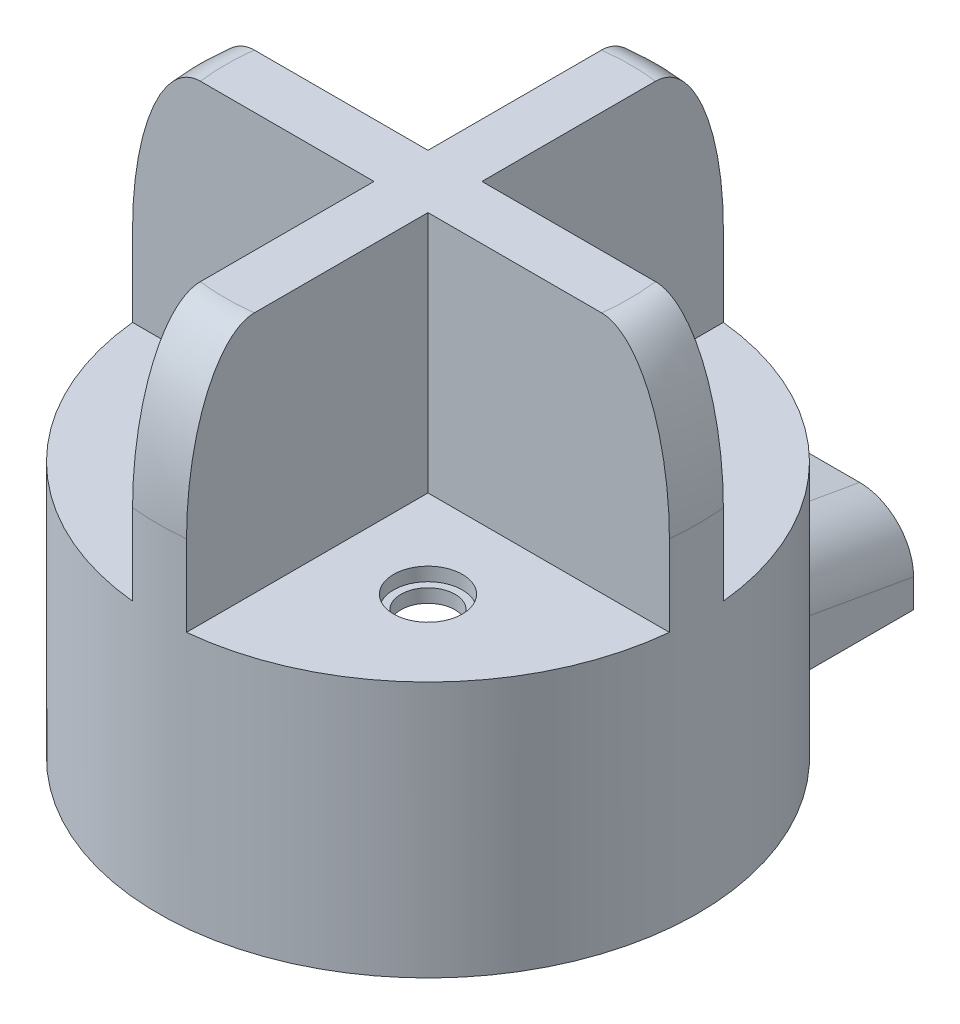
SolidWorks part; units mm, degrees
ref_plane "Front Plane" through (0, 0, 0) normal (0, 0, 1) x (1, 0, 0)
ref_plane "Top Plane" through (0, 0, 0) normal (0, 1, 0) x (1, 0, 0)
ref_plane "Right Plane" through (0, 0, 0) normal (1, 0, 0) x (0, 0, -1)
sketch "Sketch1" plane through (0, 0, 0) normal (0, 1, 0) x (1, 0, 0)
  line L0 (0, 20) -> (0, -20) construction
  line L1 (-20, 0) -> (20, 0) construction
  line L2 (-2, 20) -> (-2, 2)
  line L3 (-20, -2) -> (-2, -2)
  line L4 (2, 20) -> (2, 2)
  line L5 (-20, 2) -> (-2, 2)
  line L6 (2, 2) -> (20, 2)
  line L7 (-20, 2) -> (20, 2) construction
  line L8 (-2, -2) -> (-2, -20)
  line L9 (-2, 20) -> (-2, -20) construction
  line L10 (2, -2) -> (2, -20)
  line L11 (2, 20) -> (2, -20) construction
  line L12 (2, -2) -> (20, -2)
  line L13 (-20, -2) -> (20, -2) construction
  circle A0 centre (0, 0) radius 20
  point P6 (0, 0)
  point P9 (0, 0)
  dimension "D1" = 40
  dimension "D2" = 2
  dimension "D3" = 2
extrude "Boss-Extrude1" add sketch "Sketch1" along normal blind 2 contours A0
extrude "Boss-Extrude2" add sketch "Sketch1<3>" along normal blind 20 contours L12 A0 L6 L4 L2 L5 L3 L8 L10 region at (0, 0, 0)
sketch "Sketch1<3>" plane through (0, 0, 0) normal (0, 1, 0) x (1, 0, 0) same geometry as "Sketch1"
fillet "Fillet1" radius 12 4 edges at (-20, 20, 0) (0, 20, -20) (0, 20, 20) (20, 20, 0) second distance 5 first distance on face at (0, 0, 20)
sketch "Sketch2" plane through (0, 0, 0) normal (0, -1, 0) x (1, 0, 0)
  circle A2 centre (0, 0) radius 19
  circle A3 centre (0, 0) radius 19
  circle A4 centre (0, 0) radius 20
  circle A5 centre (0, 0) radius 20
  dimension "D1" = 1
  dimension "D2" = 0
extrude "Boss-Extrude3" add sketch "Sketch2" along normal blind 17
sketch "Sketch3" plane through (0, -17, 0) normal (0, -1, 0) x (1, 0, 0)
  line L0 (0, 20) -> (0, -20)
  circle A0 centre (0, 0) radius 20 construction
  circle A2 centre (0, 0) radius 20
  arc A3 (0, -20) -> (0, 20) centre (0, 0) ccw
  dimension "D1" = 0
extrude "Boss-Extrude4" [suppressed] add sketch "Sketch3" against normal blind 2
sketch "Sketch4" plane through (0, 2, 0) normal (0, 1, 0) x (1, 0, 0)
  line L0 (19.8997, -2) -> (2, -2) construction
  line L1 (2, -19.8997) -> (2, -2) construction
  line L2 (0, 6.0536) -> (0, 0) construction
  line L3 (0, 0) -> (5.728, 0) construction
  line L4 (-2, 14.8661) -> (-2, 2) construction
  line L5 (-2, 6.6454) -> (2, 6.6454)
  line L6 (2, 14.8661) -> (2, 2) construction
  circle A0 centre (8.5, -8.5) radius 2.55
  circle A1 centre (8.5, 8.5) radius 2.55
  circle A2 centre (-8.5, 8.5) radius 2.55
  circle A3 centre (-8.5, -8.5) radius 2.55
  dimension "D1" = 5.1
  dimension "D2" = 6.5
  dimension "D3" = 6.5
extrude "Cut-Extrude1" cut sketch "Sketch4" against normal blind 1 contours A3 | A0 | A1 | A2 region at (8.5, 2, 8.5) region at (8.5, 2, -8.5) region at (-8.5, 2, 8.5)
sketch "Sketch5" plane through (0, 0, 0) normal (0, 0, 1) x (1, 0, 0)
  line L0 (-20, -17) -> (20, -17) construction
  line L1 (-7.5, -10.5) -> (7.5, -10.5)
  line L2 (-7.5, -10.5) -> (-7.5, -17)
  line L3 (-7.5, -17) -> (7.5, -17)
  line L4 (7.5, -10.5) -> (7.5, -17)
  line L5 (-7.5, -10.5) -> (7.5, -17) construction
  line L6 (-7.5, -17) -> (7.5, -10.5) construction
  point P0 (0, -13.75)
  dimension "D1" = 15
  dimension "D2" = 6.5
extrude "Cut-Extrude2" cut sketch "Sketch5" against normal up to next
sketch "Sketch7" plane through (-7.5, 0, 0) normal (1, 0, 0) x (0, 0, -1)
  line L0 (17, -8.971) -> (27.5, -10.8225)
  line L2 (27.5, -10.8225) -> (27.5, -11.8225)
  line L3 (27.5, -11.8225) -> (17, -9.971)
  line L4 (17, -9.971) -> (17, -8.971)
  line L5 (20, -10.5) -> (20, 8) construction
  line L7 (18.5405, -10.5) -> (20, -10.5) construction
  dimension "D1" = 3
  dimension "D2" = 7.5
  dimension "D3" = 10
  dimension "D4" = 1
extrude "Boss-Extrude6" add sketch "Sketch7" along normal up to surface (15 mm away) up to face at (7.5, -13.75, -17.9988)
sketch "Sketch9" plane through (0, 0, 0) normal (0, 0, 1) x (1, 0, 0)
  line L0 (7.5, -9.2427) -> (7.5, -17)
  line L1 (7.5, -17) -> (8.5, -17)
  line L2 (-20, -17) -> (20, -17) construction
  line L3 (8.5, -17) -> (8.5, -9.2427)
  line L4 (8.5, -9.2427) -> (7.5, -9.2427)
  line L5 (0, 0) -> (0, 9.2885) construction
  line L6 (-8.5, -9.2427) -> (-7.5, -9.2427)
  line L7 (-8.5, -17) -> (-8.5, -9.2427)
  line L10 (-7.5, -17) -> (-8.5, -17)
  line L11 (-7.5, -9.2427) -> (-7.5, -17)
  dimension "D1" = 1
extrude "Boss-Extrude7" add sketch "Sketch9" against normal up to surface (27.5 mm away) up to face at (0, -11.3225, -27.5)
sketch "Sketch17" plane through (0, 0, 0) normal (0, -1, 0) x (1, 0, 0)
  circle A0 centre (0, 0) radius 19 construction
  circle A1 centre (0, 0) radius 19
extrude "Cut-Extrude6" cut sketch "Sketch17" along normal blind 49
sketch "Sketch11" plane through (0, 1, 0) normal (0, 1, 0) x (1, 0, 0)
  circle A0 centre (-8.5, -8.5) radius 2
  circle A1 centre (-8.5, -8.5) radius 2.55 construction
  dimension "D1" = 4
extrude "Cut-Extrude3" cut sketch "Sketch11" against normal through all contours A0
pattern_circular "CirPattern1" count 4 over 360 about axis through (0, 2, 0) along (0, -1, 0) of "Cut-Extrude3"
sketch "Sketch14" plane through (0, -6.7632, 1.1925) normal (0, -0.9848, 0.1736) x (1, 0, 0)
  line L0 (-7.5, -30.0342) -> (-7.5, -20.1439) construction
  line L1 (-7.5, -20.7753) -> (7.5, -20.7753)
  line L2 (-7.5, -20.7753) -> (-7.5, -7.9571)
  line L3 (-7.5, -7.9571) -> (7.5, -7.9571)
  line L4 (7.5, -20.7753) -> (7.5, -7.9571)
  line L5 (7.5, -20.0374) -> (7.5, -29.1352) construction
extrude "Cut-Extrude4" cut sketch "Sketch14" along normal blind 10 contours L2 L3 L4 L1
other "DeleteFace1" face at (8.0007, -9.2427, -22.9128) face at (-8.0007, -9.2427, -22.9128) face at (-7.5, -9.7693, -24.5135) face at (7.5, -9.7693, -24.5135) and patch yes
fillet "Fillet2" radius 4 4 edges at (7.5, -10.937, -22.4785) (-7.5, -10.937, -22.4785) (-8.5, -9.9941, -22.8019) (8.5, -9.9941, -22.8019)
other "DeleteFace4" face at (-2.741, -10.4955, -19.779) face at (2.4736, -10.4773, -19.8322) face at (0, -10.5, -19.5605) face at (0, -10.4193, -19.2586) and patch yes
sketch "Sketch15" plane through (0, -17, 0) normal (0, -1, 0) x (1, 0, 0)
  line L0 (-8.5, -18.1039) -> (-8.5, -27.5) construction
  line L1 (-8.5, -21.1) -> (-8.5, -19.9)
  line L2 (-8.5, -27.5) -> (-4.5, -27.5) construction
  arc A0 (-8.5, -21.1) -> (-8.5, -19.9) centre (-8.5, -20.5) ccw
  dimension "D1" = 0.6
  dimension "D2" = 7
extrude "Cut-Extrude5" cut sketch "Sketch15" against normal through all both and the other way through all
sketch "Sketch18" plane through (0, 0, 0) normal (0, 0, 1) x (1, 0, 0)
  line L0 (-20, 0) -> (20, 0)
  line L1 (-20, 8) -> (-20, -17) construction
  line L2 (20, -17) -> (20, 8) construction
  line L3 (-19, 0) -> (19, 0) construction
  point P2 (-19.9448, -0.6835)
  point P5 (0, 0)
  point P6 (0, 0)
  point P9 (0, 0)
